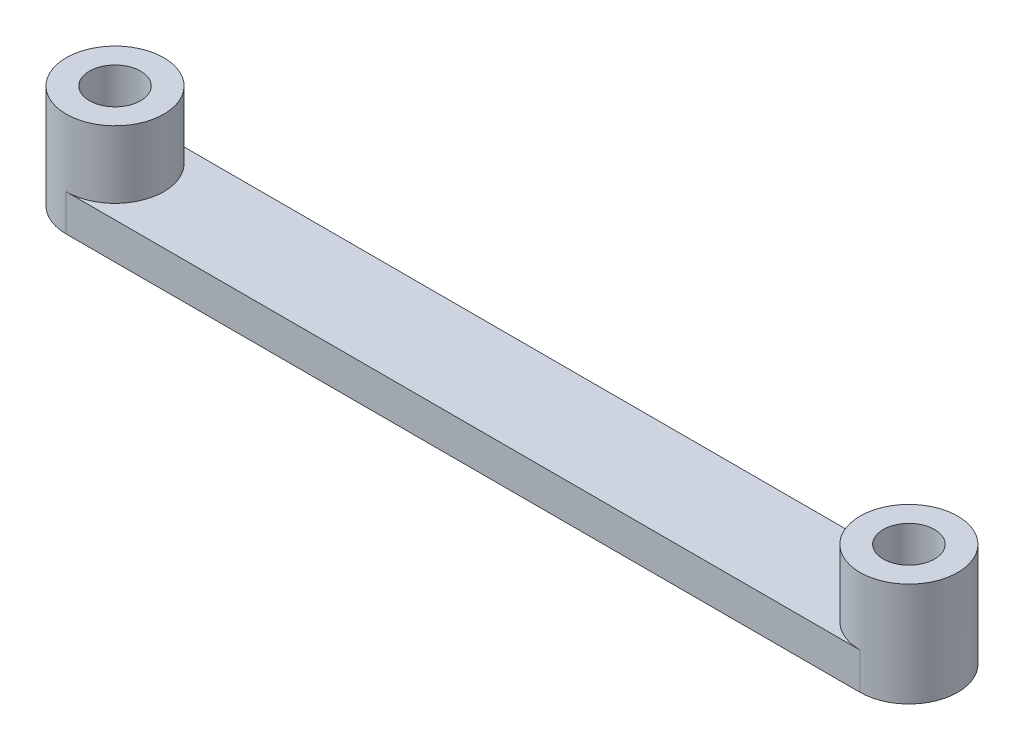
SolidWorks part; units mm, degrees
ref_plane "前视基准面" through (0, 0, 0) normal (0, 0, 1) x (1, 0, 0)
ref_plane "上视基准面" through (0, 0, 0) normal (0, 1, 0) x (1, 0, 0)
ref_plane "右视基准面" through (0, 0, 0) normal (1, 0, 0) x (0, 0, -1)
sketch "Sketch1" plane through (0, 0, 0) normal (0, 1, 0) x (1, 0, 0)
  line L0 (0, 0) -> (65, 0) construction
  line L1 (0, 4) -> (65, 4)
  line L2 (0, -4) -> (65, -4)
  arc A0 (0, 4) -> (0, -4) centre (0, 0) ccw
  arc A1 (65, -4) -> (65, 4) centre (65, 0) ccw
  point P3 (32.5, 0)
  dimension "D2" = 4
  dimension "D1" = 65
extrude "Boss-Extrude1" add sketch "Sketch1" along normal blind 3
sketch "Sketch3" plane through (0, 3, 0) normal (0, 1, 0) x (1, 0, 0)
  circle A0 centre (0, 0) radius 4
  circle A1 centre (65, 0) radius 4
  dimension "D1" = 8
  dimension "D2" = 8
extrude "Boss-Extrude2" add sketch "Sketch3" along normal blind 5.5
sketch "Sketch4" plane through (0, 8.5, 0) normal (0, 1, 0) x (1, 0, 0)
  circle A0 centre (0, 0) radius 2.1
  circle A1 centre (65, 0) radius 2.1
  dimension "D1" = 4.2
  dimension "D2" = 4.2
extrude "Cut-Extrude1" cut sketch "Sketch4" against normal through all
